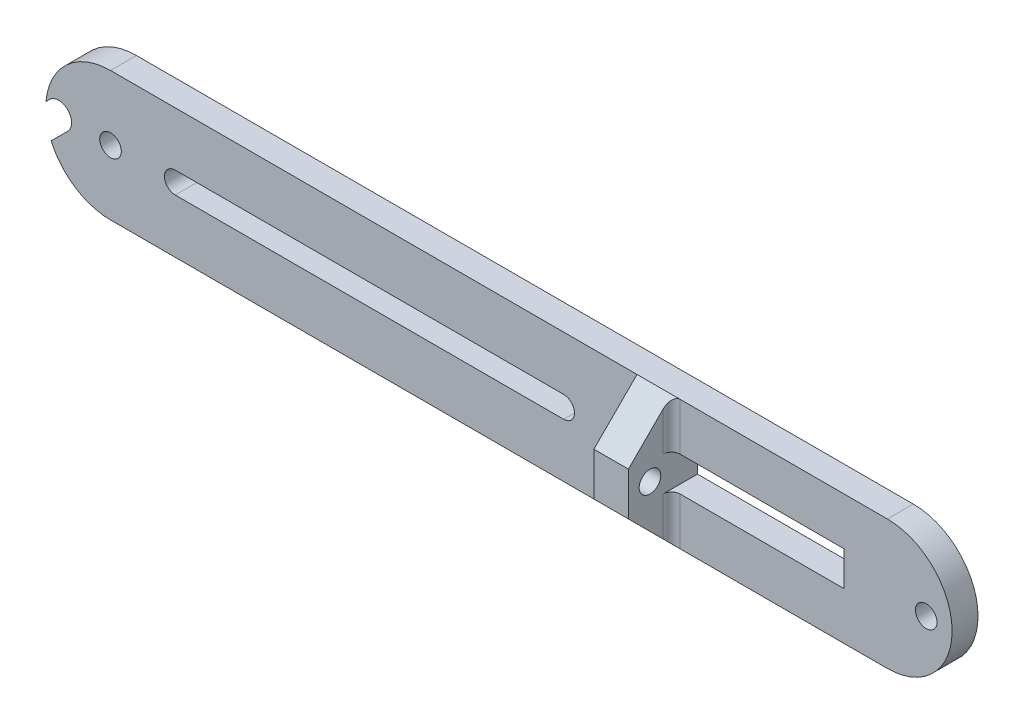
SolidWorks part; units mm, degrees
ref_plane "Plan de face" through (0, 0, 0) normal (0, 0, 1) x (1, 0, 0)
ref_plane "Plan de dessus" through (0, 0, 0) normal (0, 1, 0) x (1, 0, 0)
ref_plane "Plan de droite" through (0, 0, 0) normal (1, 0, 0) x (0, 0, -1)
sketch "Esquisse1" plane through (0, 0, 0) normal (0, 0, 1) x (1, 0, 0)
  line L0 (-74.3787, 0) -> (69.7437, 0) construction
  line L1 (0, 0) -> (0, 19.0596) construction
  line L2 (90, -15) -> (-90, -15)
  line L3 (90, 15) -> (-90, 15)
  line L4 (15, -2.5) -> (-75, -2.5)
  line L5 (40, -4) -> (80, -4)
  line L6 (40, -4) -> (40, 4)
  line L7 (40, 4) -> (80, 4)
  line L8 (80, -4) -> (80, 4)
  line L9 (40, -4) -> (80, 4) construction
  line L10 (40, 4) -> (80, -4) construction
  line L11 (-75, 2.5) -> (15, 2.5)
  arc A0 (90, -15) -> (90, 15) centre (90, 0) ccw
  circle A1 centre (99, 0) radius 2.5
  circle A2 centre (-90, 0) radius 2.5
  arc A3 (-90, -15) -> (-90, 15) centre (-90, 0) cw
  arc A5 (-75, 2.5) -> (-75, -2.5) centre (-75, 0) ccw
  arc A6 (15, -2.5) -> (15, 2.5) centre (15, 0) ccw
  point P4 (60, 0)
  point P17 (0, -15)
  point P20 (0, 15)
  dimension "D1" = 30
  dimension "D3" = 5
  dimension "D2" = 9
  dimension "D4" = 8
  dimension "D5" = 40
  dimension "D6" = 60
extrude "Boss.-Extru.1" add sketch "Esquisse1" along normal blind 6
sketch "Esquisse2" plane through (40, 0, 0) normal (1, 0, 0) x (0, 0, -1)
  line L0 (0, -4) -> (-6, 4) construction
  line L1 (-6, 4) -> (-6, 0) construction
  line L2 (-6, 4) -> (-6, -4) construction
  line L3 (-6, 0) -> (-15.5036, 0) construction
  line L4 (-6, 15) -> (-6, -15) construction
  line L6 (-16, 5) -> (-16, -5)
  line L8 (-6, 5) -> (-6, -5)
  line L9 (-16, 5) -> (-6, -5) construction
  line L10 (-16, -5) -> (-6, 5) construction
  line L11 (-6, -15) -> (-16, -5)
  line L12 (-6, -15) -> (-6, -5)
  line L13 (-6, 5) -> (-6, 15)
  line L14 (-6, 15) -> (-16, 5)
  circle A0 centre (-11, 0) radius 2.5
  point P7 (-11, 0)
  dimension "D3" = 5
  dimension "D1" = 10
  dimension "D2" = 10
extrude "Boss.-Extru.2" add sketch "Esquisse2" against normal blind 8
fillet "Congé2" radius 2 2 edges
sketch "Esquisse3" plane through (32, 0, 0) normal (-1, 0, 0) x (0, 0, 1)
  line L0 (11, 0) -> (11, 4) construction
  line L1 (11, 0) -> (14.4641, 2) construction
  line L2 (11, 0) -> (14.4641, -2) construction
  line L3 (11, 4) -> (14.4641, 2)
  line L4 (14.4641, 2) -> (14.4641, -2)
  line L5 (14.4641, -2) -> (11, -4)
  line L6 (7.5359, 2) -> (7.5359, -2)
  line L7 (11, 4) -> (7.5359, 2)
  line L8 (7.5359, -2) -> (11, -4)
  dimension "D2" = 60
  dimension "D3" = 60
extrude "Enlèv. mat.-Extru.1" cut sketch "Esquisse3" against normal blind 4
sketch "Esquisse4" plane through (0, 0, 6) normal (0, 0, 1) x (1, 0, 0)
  line L0 (-90, 0) -> (-105, 0) construction
  line L1 (-105, 0) -> (-102, 0) construction
  line L2 (-102, 0) -> (-99.8787, -2.1213) construction
  line L3 (-99.8787, -2.1213) -> (-104.1213, 2.1213)
  line L4 (-99.8787, -2.1213) -> (-104.1213, 2.1213)
  line L5 (-99.8787, -2.1213) -> (-104.2614, -6.504)
  line L6 (-104.1213, 2.1213) -> (-108.504, -2.2614)
  line L7 (-104.2614, -6.504) -> (-108.504, -2.2614)
  arc A0 (-90, 15) -> (-90, -15) centre (-90, 0) ccw construction
  circle A1 centre (-102, 0) radius 3
  arc M9 (-90, 15) -> (-90, -15) centre (-90, 0) ccw
  dimension "D1" = 3
  dimension "D2" = 135
extrude "Enlèv. mat.-Extru.4" cut sketch "Esquisse4" against normal blind 10 contours L3 A1 | A1 L6 M9 | A1 L5 M9 | L3 A1 region at (-102.9003, -0.9003, 6) region at (-101.0997, 0.9003, 6) region at (-103.2777, -3.6386, 6) region at (-104.7977, 1.1965, 6)
